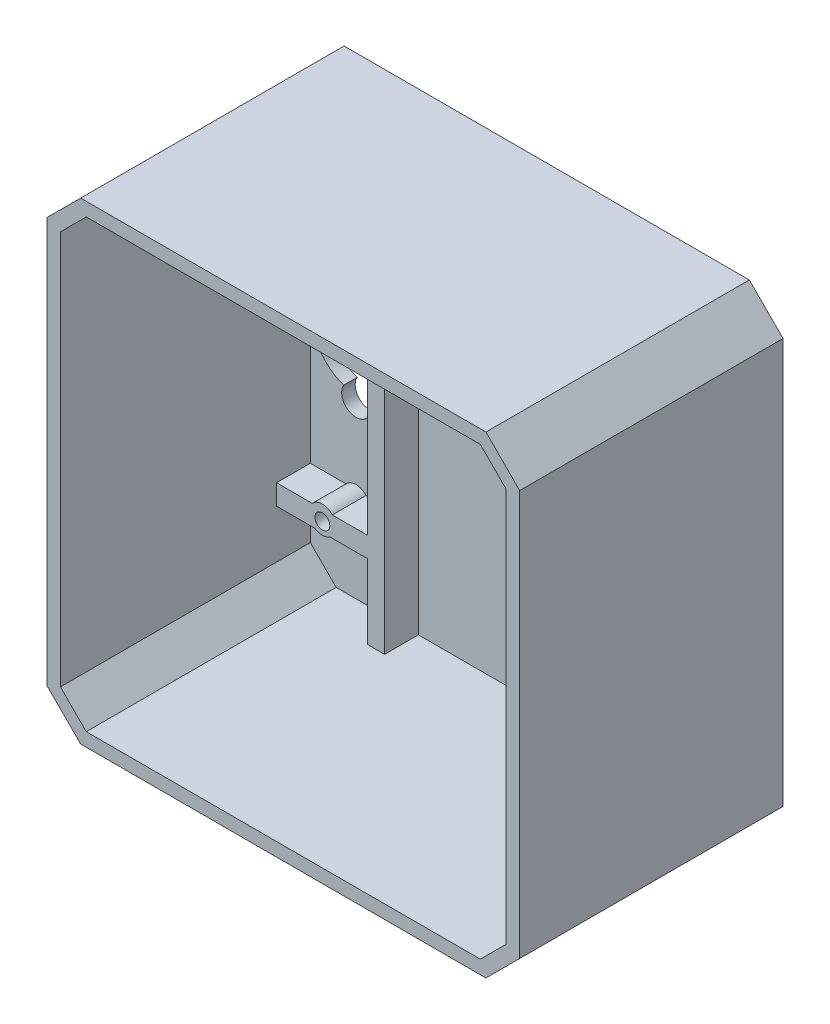
SolidWorks part; units mm, degrees
ref_plane "Front Plane" through (0, 0, 0) normal (0, 0, 1) x (1, 0, 0)
ref_plane "Top Plane" through (0, 0, 0) normal (0, 1, 0) x (1, 0, 0)
ref_plane "Right Plane" through (0, 0, 0) normal (1, 0, 0) x (0, 0, -1)
sketch "Sketch1" plane through (0, 0, 0) normal (0, 0, 1) x (1, 0, 0)
  line L1 (51.8222, 34.9266) -> (121.8222, 34.9266)
  line L2 (51.8222, 34.9266) -> (51.8222, -35.0734)
  line L3 (51.8222, -35.0734) -> (121.8222, -35.0734)
  line L4 (121.8222, 34.9266) -> (121.8222, -35.0734)
  dimension "D1" = 70
  dimension "D2" = 70
ref_plane "Plane1" through (0, 0, -39) normal (0, 0, 1) x (1, 0, 0)
extrude "Boss-Extrude1" add sketch "Sketch1" against normal blind 39
chamfer "Chamfer1" distance 5 angle 45 4 edges at (121.8222, -35.0734, -19.5) (51.8222, -35.0734, -19.5) (51.8222, 34.9266, -19.5) (121.8222, 34.9266, -19.5)
shell "Shell1" thickness 2 removed face at (86.8222, -0.0734, 0)
sketch "Sketch3" plane through (0, 0, -37) normal (0, 0, 1) x (1, 0, 0)
  line L0 (115.9938, 32.9266) -> (57.6506, 32.9266) construction
  line L1 (67.3222, 32.9266) -> (69.8222, 32.9266)
  line L2 (67.3222, 32.9266) -> (67.3222, -33.0734)
  line L3 (67.3222, -33.0734) -> (69.8222, -33.0734)
  line L4 (69.8222, 32.9266) -> (69.8222, -33.0734)
  line L5 (57.6506, -33.0734) -> (115.9938, -33.0734) construction
  line L6 (53.8222, 29.0982) -> (53.8222, -29.2449) construction
  line L8 (86.8222, 32.9266) -> (86.8222, -50.5449) construction
  line L9 (106.3222, -33.0734) -> (103.8222, -33.0734)
  line L10 (103.8222, 32.9266) -> (103.8222, -33.0734)
  line L11 (106.3222, 32.9266) -> (103.8222, 32.9266)
  line L12 (106.3222, 32.9266) -> (106.3222, -33.0734)
  dimension "D1" = 2.5
  dimension "D2" = 13.5
extrude "Boss-Extrude2" add sketch "Sketch3" along normal blind 5
sketch "Sketch4" plane through (0, 0, -37) normal (0, 0, 1) x (1, 0, 0)
  line L0 (53.8222, 29.0982) -> (53.8222, -29.2449) construction
  line L1 (53.8222, -19.0734) -> (67.3222, -19.0734)
  line L2 (53.8222, -19.0734) -> (53.8222, -22.0734)
  line L3 (53.8222, -22.0734) -> (67.3222, -22.0734)
  line L4 (67.3222, -19.0734) -> (67.3222, -22.0734)
  line L5 (67.3222, 32.9266) -> (67.3222, -33.0734) construction
  line L6 (57.6506, -33.0734) -> (67.3222, -33.0734) construction
  line L7 (53.8222, 29.0982) -> (53.8222, -29.2449) construction
  line L8 (53.8222, 9.9266) -> (67.3222, 9.9266)
  line L9 (53.8222, 9.9266) -> (53.8222, 6.9266)
  line L10 (53.8222, 6.9266) -> (67.3222, 6.9266)
  line L11 (67.3222, 9.9266) -> (67.3222, 6.9266)
  line L12 (86.8222, 32.9266) -> (86.8222, -49.2759) construction
  line L13 (103.8222, 32.9266) -> (69.8222, 32.9266) construction
  line L14 (119.8222, -22.0734) -> (106.3222, -22.0734)
  line L15 (106.3222, -19.0734) -> (106.3222, -22.0734)
  line L16 (119.8222, -19.0734) -> (106.3222, -19.0734)
  line L17 (119.8222, -19.0734) -> (119.8222, -22.0734)
  line L18 (119.8222, 6.9266) -> (106.3222, 6.9266)
  line L19 (106.3222, 9.9266) -> (106.3222, 6.9266)
  line L20 (119.8222, 9.9266) -> (106.3222, 9.9266)
  line L21 (119.8222, 9.9266) -> (119.8222, 6.9266)
  dimension "D1" = 3
  dimension "D2" = 14
  dimension "D3" = 26
  dimension "D4" = 3
extrude "Boss-Extrude3" add sketch "Sketch4" along normal up to surface (5 mm away) up to face at (68.5722, -0.0734, -32)
sketch "Sketch5" plane through (0, 0, -37) normal (0, 0, 1) x (1, 0, 0)
  line L0 (67.3222, 9.9266) -> (53.8222, 9.9266) construction
  line L1 (67.3222, 9.9266) -> (53.8222, 9.9266)
  line L2 (67.3222, 9.9266) -> (67.3222, 15.4266)
  line L3 (67.3222, 15.4266) -> (53.8222, 15.4266)
  line L4 (53.8222, 9.9266) -> (53.8222, 15.4266)
  line L5 (53.8222, 29.0982) -> (53.8222, -29.2449) construction
  dimension "D1" = 5.5
extrude "Cut-Extrude1" cut sketch "Sketch5" against normal through all
sketch "Sketch6" plane through (0, 0, -37) normal (0, 0, 1) x (1, 0, 0)
  line L0 (86.8222, 32.9266) -> (86.8222, -44.1182) construction
  line L1 (53.8222, 6.9266) -> (67.3222, 6.9266) construction
  line L2 (103.8222, 32.9266) -> (69.8222, 32.9266) construction
  circle A0 centre (60.5866, -0.5734) radius 6.25
  circle A1 centre (113.0578, -0.5734) radius 6.25
  point P7 (60.5722, 6.9266)
  dimension "D1" = 12.5
  dimension "D2" = 7.5
extrude "Cut-Extrude2" cut sketch "Sketch6" against normal through all
sketch "Sketch8" plane through (0, 0, -37) normal (0, 0, 1) x (1, 0, 0)
  line L0 (58.7923, -6.5603) -> (62.3844, -6.5592)
  line L1 (86.8222, -35.0734) -> (86.8222, -45.0028) construction
  line L2 (56.8222, -35.0734) -> (116.8222, -35.0734) construction
  line L3 (114.8521, -6.5603) -> (111.26, -6.5592)
  arc A4 (58.7923, -6.5603) -> (62.3844, -6.5592) centre (60.5887, -7.686) ccw
  circle A5 centre (60.5866, -0.5734) radius 6.25 construction
  arc A6 (114.8521, -6.5603) -> (111.26, -6.5592) centre (113.0557, -7.686) cw
extrude "Cut-Extrude3" cut sketch "Sketch8" against normal blind 10
sketch "Sketch9" plane through (0, 0, -32) normal (0, 0, 1) x (1, 0, 0)
  line L0 (86.8222, -35.0734) -> (86.8222, -43.4105) construction
  line L1 (56.8222, -35.0734) -> (116.8222, -35.0734) construction
  circle A0 centre (60.5935, 8.4008) radius 2
  circle A1 centre (60.5935, -20.415) radius 2
  circle A2 centre (113.0508, -20.415) radius 2
  circle A3 centre (113.0508, 8.4008) radius 2
extrude "Boss-Extrude4" add sketch "Sketch9" against normal up to surface (5 mm away) up to face at (60.587, -2.0647, -37)
sketch "Sketch10" plane through (0, 0, -32) normal (0, 0, 1) x (1, 0, 0)
  line L0 (86.8222, -35.0734) -> (86.8222, -48.0105) construction
  line L1 (56.8222, -35.0734) -> (116.8222, -35.0734) construction
  circle A0 centre (60.6065, 8.3099) radius 1.1
  circle A1 centre (60.6065, -20.633) radius 1.1
  circle A2 centre (113.0379, -20.633) radius 1.1
  circle A3 centre (113.0379, 8.3099) radius 1.1
extrude "Cut-Extrude4" cut sketch "Sketch10" against normal blind 4
